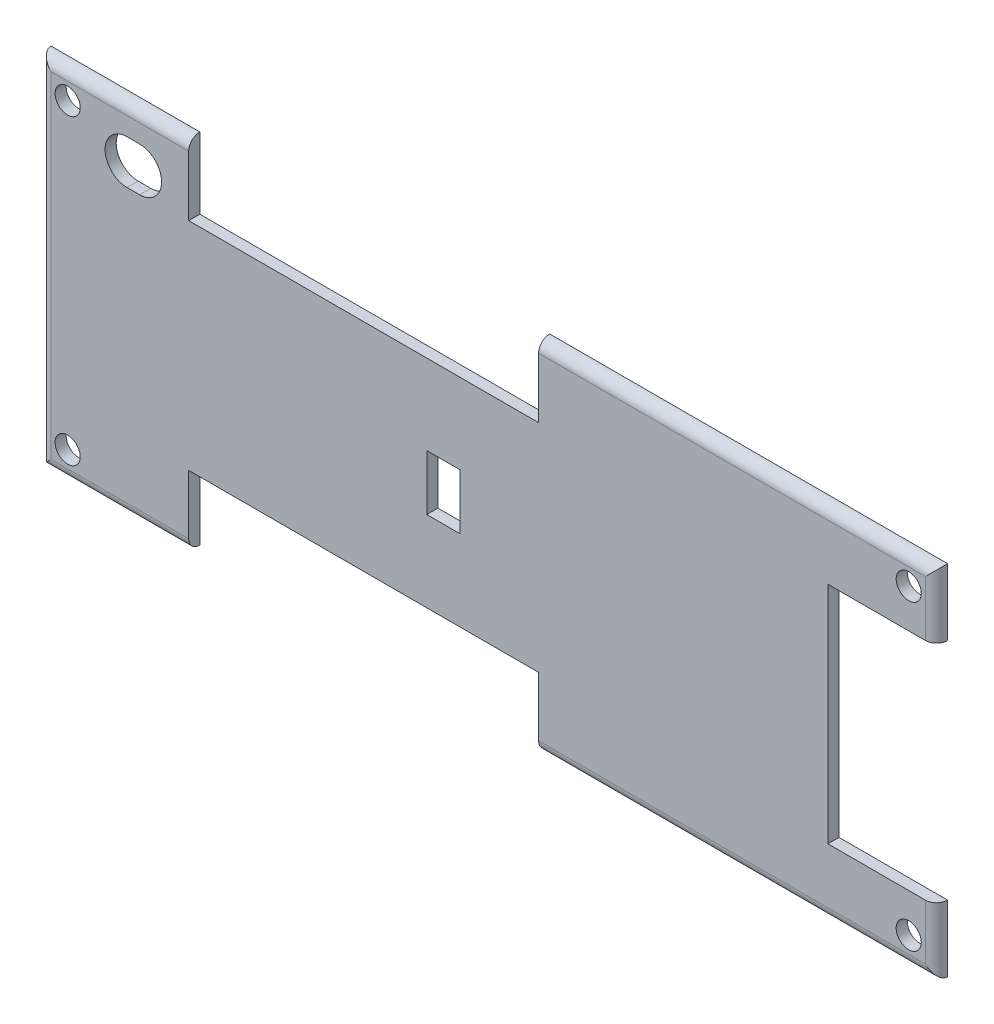
SolidWorks part; units mm, degrees
ref_plane "Front Plane" through (0, 0, 0) normal (0, 0, 1) x (1, 0, 0)
ref_plane "Top Plane" through (0, 0, 0) normal (0, 1, 0) x (1, 0, 0)
ref_plane "Right Plane" through (0, 0, 0) normal (1, 0, 0) x (0, 0, -1)
sketch "Sketch1" plane through (0, 0, 0) normal (0, 0, 1) x (1, 0, 0)
  line L0 (-26.65, 16.1) -> (-40.0322, 16.1)
  line L1 (-40.0322, 16.1) -> (-40.0322, -16.08)
  line L2 (-40.0322, -16.08) -> (-26.65, -16.08)
  line L3 (-26.65, -16.08) -> (-26.65, -9.7522)
  line L4 (-26.65, -14.18) -> (-26.65, 14.2) construction
  line L5 (-26.65, -9.7522) -> (4.81, -9.7522)
  line L6 (4.81, -9.7522) -> (4.81, -16.08)
  line L7 (4.81, -16.08) -> (40.5907, -16.08)
  line L8 (40.5907, -16.08) -> (40.5907, -10.0958)
  line L9 (40.5907, -10.0958) -> (30.8222, -10.0958)
  line L10 (30.8222, -10.0958) -> (30.8222, 10.1158)
  line L11 (30.8222, 10.1158) -> (40.5907, 10.1158)
  line L12 (40.5907, 10.1158) -> (40.5907, 16.1)
  line L13 (40.5907, 16.1) -> (4.81, 16.1)
  line L14 (4.81, 16.1) -> (4.81, 9.6939)
  line L15 (4.81, 9.6939) -> (-26.65, 9.6939)
  line L17 (-26.65, 9.6939) -> (-26.65, 16.1)
  line L18 (-32.1906, 11.4763) -> (-31.0618, 11.4763) construction
  line L19 (-5.2439, 2.49) -> (-2.26, 2.49)
  line L20 (-5.2439, 2.49) -> (-5.2439, -2.49)
  line L21 (-5.2439, -2.49) -> (-2.26, -2.49)
  line L22 (-2.26, 2.49) -> (-2.26, -2.49)
  line L23 (-5.2439, 2.49) -> (-2.26, -2.49) construction
  line L24 (-5.2439, -2.49) -> (-2.26, 2.49) construction
  line L25 (-32.1906, 13.4517) -> (-31.0618, 13.4517)
  line L26 (-32.1906, 9.5009) -> (-31.0618, 9.5009)
  line L27 (-10.95, 16.1) -> (-26.65, 16.1) construction
  line L28 (40.5907, 10.27) -> (40.5907, -10.25) construction
  line L29 (-26.65, -16.08) -> (-10.95, -16.08) construction
  arc A0 (-32.1906, 13.4517) -> (-32.1906, 9.5009) centre (-32.1906, 11.4763) ccw
  arc A1 (-31.0618, 9.5009) -> (-31.0618, 13.4517) centre (-31.0618, 11.4763) ccw
  arc A2 (-31.62, 9.47) -> (-31.62, 13.53) centre (-31.62, 11.5) ccw construction
  circle A3 centre (-37.5322, 13.6) radius 1.1303
  circle A4 centre (-37.5322, -13.58) radius 1.1303
  circle A5 centre (38.0907, 13.6) radius 1.1303
  circle A6 centre (38.0907, -13.58) radius 1.1303
  point P28 (-3.752, 0)
  point P37 (-31.6262, 11.4763)
  point P57 (0, 0)
  point P58 (4.81, 9.5009)
  point P59 (0, 0)
  point P62 (0, 0)
  point P65 (0, 0)
  point P66 (0, 0)
  point P69 (0, 0)
  point P70 (0, 0)
  dimension "D1" = 2.2606
extrude "Boss-Extrude1" add sketch "Sketch1" along normal blind 1
fillet "Fillet1" radius 1 7 edges at (40.5907, 13.1079, 1) (22.7003, 16.1, 1) (40.5907, -13.0879, 1) (22.7003, -16.08, 1) (-33.3411, -16.08, 1) (-40.0322, 0.01, 1) (-33.3411, 16.1, 1)
